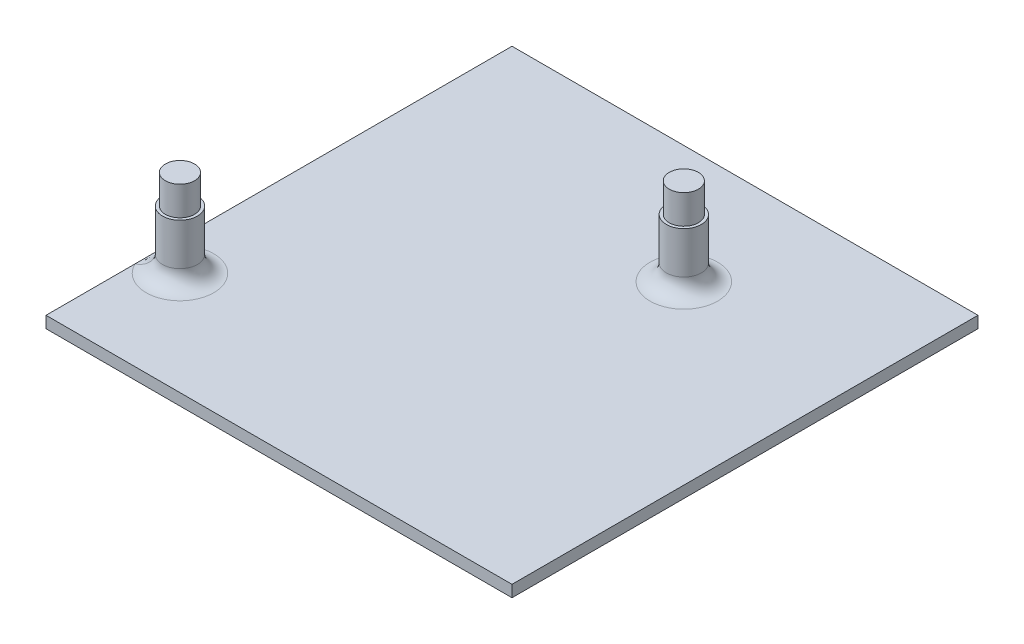
SolidWorks part; units mm, degrees
ref_plane "Front Plane" through (0, 0, 0) normal (0, 0, 1) x (1, 0, 0)
ref_plane "Top Plane" through (0, 0, 0) normal (0, 1, 0) x (1, 0, 0)
ref_plane "Right Plane" through (0, 0, 0) normal (1, 0, 0) x (0, 0, -1)
sketch "Sketch1" plane through (0, 0, 0) normal (0, 1, 0) x (1, 0, 0)
  line L0 (-27.5, 27.5) -> (-27.5, 40)
  line L1 (-27.5, 27.5) -> (27.5, 27.5)
  line L2 (-27.5, 27.5) -> (-27.5, -27.5)
  line L3 (-27.5, -27.5) -> (27.5, -27.5)
  line L4 (27.5, 27.5) -> (27.5, -27.5)
  line L5 (-27.5, 27.5) -> (27.5, -27.5) construction
  line L6 (-27.5, -27.5) -> (27.5, 27.5) construction
  line L7 (-27.5, 40) -> (52.5, 40)
  line L8 (-27.5, -27.5) -> (-27.5, -40)
  line L9 (-27.5, -40) -> (52.5, -40)
  line L10 (52.5, 40) -> (52.5, -40)
  line L11 (-27.5, -40) -> (-27.5, -27.5)
  circle A0 centre (22.25, -19.75) radius 2.5 construction
  circle A1 centre (-22.25, 22.25) radius 2.5 construction
  point P0 (0, 0)
  point P14 (52.5, 0)
  dimension "D5" = 5
  dimension "D1" = 55
  dimension "D2" = 5.25
  dimension "D3" = 19.75
  dimension "D4" = 5.25
  dimension "D6" = 80
  dimension "D7" = 80
extrude "Boss-Extrude1" add sketch "Sketch1" along normal blind 2 contours L10 L7 L0 L1 L4 L3 L8 L9 | L4 L1 L2 L3 region at (-26.3686, 0, -33.75) region at (0, 0, 0)
sketch "Sketch2" plane through (0, 2, 0) normal (0, 1, 0) x (1, 0, 0)
  circle A0 centre (-22.25, -22.25) radius 3
  circle A1 centre (22.25, 19.75) radius 3
  dimension "D5" = 6
  dimension "D6" = 6
  dimension "D1" = 22.25
  dimension "D2" = 19.75
  dimension "D3" = 22.25
  dimension "D4" = 22.25
extrude "Boss-Extrude2" add sketch "Sketch2" along normal blind 10
fillet "Fillet1" radius 2.8 2 edges at (22.25, 2, -16.75) (-22.25, 2, 25.25)
sketch "Sketch3" plane through (0, 12, 0) normal (0, 1, 0) x (1, 0, 0)
  circle A0 centre (-22.25, -22.25) radius 2.5
  circle A1 centre (22.25, 19.75) radius 2.5
  dimension "D1" = 5
extrude "Boss-Extrude3" add sketch "Sketch3" along normal blind 5
